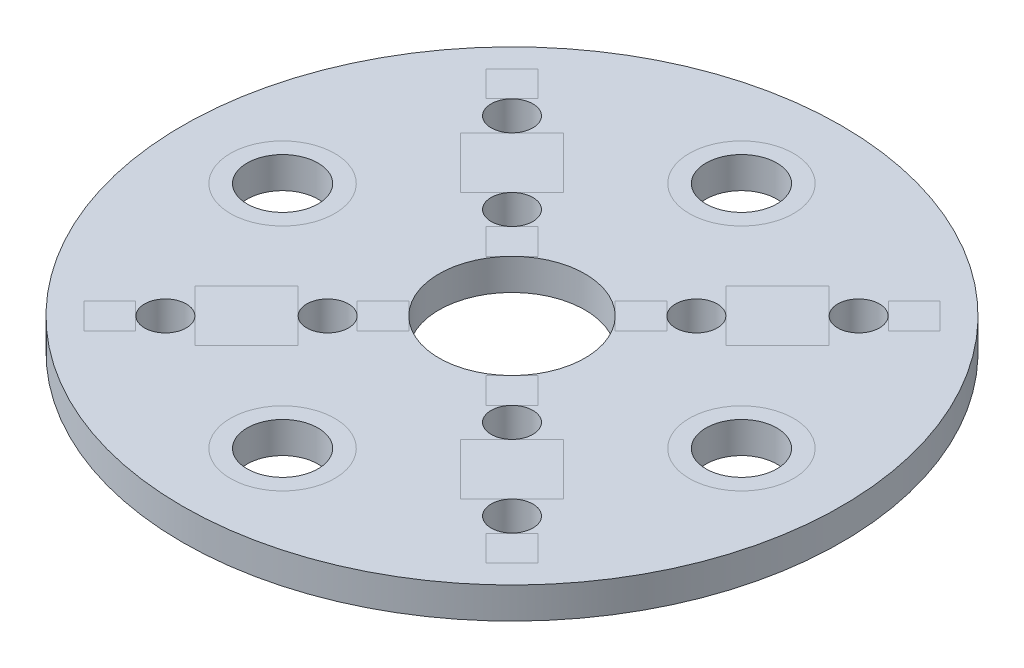
SolidWorks part; units mm, degrees
material "FR4 185HR (ISO)"
ref_plane "Front Plane" through (0, 0, 0) normal (0, 0, 1) x (1, 0, 0)
ref_plane "Top Plane" through (0, 0, 0) normal (0, 1, 0) x (1, 0, 0)
ref_plane "Right Plane" through (0, 0, 0) normal (1, 0, 0) x (0, 0, -1)
sketch "Sketch1" plane through (0, 0, 0) normal (0, 1, 0) x (1, 0, 0)
  line L0 (-3.75, -6.9532) -> (-3.75, -14.65)
  line L1 (-3.75, -14.65) -> (3.75, -14.65)
  line L2 (3.75, -14.65) -> (3.75, -6.9532)
  line L3 (0, 0) -> (0, -14.65) construction
  line L4 (0, 0) -> (7.9, 0) construction
  line L5 (-1.2374, 1.2374) -> (-5.5861, 5.5861) construction
  line L6 (-5.5, 0) -> (0, 5.5) construction
  line L7 (-1.4907, 5.3329) -> (-5.3329, 1.4907) construction
  line L8 (1.0607, -4.4393) -> (3.6352, -7.0139) construction
  line L9 (-1.0607, -4.4393) -> (-3.6352, -7.0139) construction
  line L10 (-4.4393, 1.0607) -> (-7.0139, 3.6352) construction
  line L11 (-4.4393, -1.0607) -> (-7.0139, -3.6352) construction
  line L12 (1.0607, 4.4393) -> (3.6352, 7.0139) construction
  line L13 (-1.0607, 4.4393) -> (-3.6352, 7.0139) construction
  line L14 (4.4393, -1.0607) -> (7.0139, -3.6352) construction
  line L15 (4.4393, 1.0607) -> (7.0139, 3.6352) construction
  line L16 (-2.6754, 2.0274) -> (-1.6291, -0.6392) construction
  line L17 (-2.0274, 2.6754) -> (0.6392, 1.6291) construction
  line L18 (-4.7962, 4.1481) -> (-6.3165, 4.7447) construction
  line L19 (-4.1481, 4.7962) -> (-4.7447, 6.3165) construction
  line L20 (1.2374, 1.2374) -> (5.5861, 5.5861) construction
  line L21 (0, 5.5) -> (5.5, 0) construction
  line L22 (5.3329, 1.4907) -> (1.4907, 5.3329) construction
  line L23 (1.2374, -1.2374) -> (5.5861, -5.5861) construction
  line L24 (5.5, 0) -> (0, -5.5) construction
  line L25 (1.4907, -5.3329) -> (5.3329, -1.4907) construction
  line L26 (-1.2374, -1.2374) -> (-5.5861, -5.5861) construction
  line L27 (0, -5.5) -> (-5.5, 0) construction
  line L28 (-5.3329, -1.4907) -> (-1.4907, -5.3329) construction
  line L29 (0, -10.75) -> (2.95, -10.75) construction
  line L30 (0, -10.75) -> (-2.95, -10.75) construction
  arc A0 (3.75, -6.9532) -> (-3.75, -6.9532) centre (0, 0) ccw
  circle A1 centre (5.5, 0) radius 1.5 construction
  circle A2 centre (5.5, 0) radius 0.85
  circle A3 centre (0, -5.5) radius 0.85
  circle A4 centre (0, -5.5) radius 1.5 construction
  circle A5 centre (-5.5, 0) radius 0.85
  circle A6 centre (-5.5, 0) radius 1.5 construction
  circle A7 centre (0, 5.5) radius 0.85
  circle A8 centre (0, 5.5) radius 1.5 construction
  circle A9 centre (0, 0) radius 1.75
  arc A10 (-3.75, -6.9532) -> (3.75, -6.9532) centre (0, 0) ccw construction
  circle A11 centre (-4.154, 4.154) radius 0.5
  circle A12 centre (-2.21, 2.21) radius 0.5
  circle A13 centre (4.154, 4.154) radius 0.5
  circle A14 centre (2.21, 2.21) radius 0.5
  circle A15 centre (4.154, -4.154) radius 0.5
  circle A16 centre (2.21, -2.21) radius 0.5
  circle A17 centre (-4.154, -4.154) radius 0.5
  circle A18 centre (-2.21, -2.21) radius 0.5
  circle A19 centre (-3, 0) radius 0.25
  circle A20 centre (-1.5, -10.75) radius 0.25
  circle A21 centre (3, 0) radius 0.25
  circle A22 centre (1.5, -10.75) radius 0.25
  circle A23 centre (-6.2, 2.25) radius 0.25
  circle A24 centre (0, -9.75) radius 0.25
  circle A25 centre (0, -7.75) radius 0.25
  circle A26 centre (-1, -8.75) radius 0.25
  circle A27 centre (1, -8.75) radius 0.25
  circle A28 centre (-5.9, 3.55) radius 0.25
  circle A29 centre (6.2, 2.25) radius 0.25
  circle A30 centre (5.9, 3.55) radius 0.25
  point P23 (0, 0)
  point P24 (-3.4118, 3.4118)
  point P47 (0, 0)
  point P92 (0, 0)
  point P114 (0, 0)
  point P117 (0, 0)
  dimension "D5" = 3
  dimension "D6" = 1.7
  dimension "D8" = 3.5
  dimension "D11" = 1
  dimension "D12" = 1
  dimension "D16" = 5.5
  dimension "D18" = 0.5
  dimension "D23" = 8.75
  dimension "D15" = 7.75
  dimension "D22" = 9.75
  dimension "D19" = 3.9
  dimension "D20" = 3
  dimension "D24" = 0.5
  dimension "D13" = 2.21
  dimension "D14" = 4.154
  dimension "D26" = 2.25
  dimension "D27" = 0.5
  dimension "D28" = 6.2
  dimension "D29" = 5.9
  dimension "D30" = 3.55
  dimension "D31" = 0.5
  dimension "D2" = 7.5
  dimension "D3" = 14.65
  dimension "D4" = 90
  dimension "D9" = 45
  dimension "D17" = 4
  dimension "D21" = 1.5
  dimension "D25" = 1
  dimension "D7" = 4
  dimension "D10" = 4
extrude "Boss-Extrude1" add sketch "Sketch1" along normal blind 0.75
sketch "Sketch2" plane through (0, 0.75, 0) normal (0, 1, 0) x (1, 0, 0)
  line L0 (-4.154, -4.154) -> (-2.21, -2.21) construction
  line L1 (-2.7577, -4.5962) -> (-1.7678, -3.6063)
  line L2 (-1.7678, -3.6063) -> (-3.1113, -2.2628)
  line L3 (-3.1113, -2.2628) -> (-4.1012, -3.2527)
  line L4 (-4.1012, -3.2527) -> (-2.7577, -4.5962)
  line L5 (4.154, -4.154) -> (-4.154, 4.154) construction
  line L6 (4.5962, 2.7577) -> (3.6063, 1.7678)
  line L7 (3.2527, 4.1012) -> (4.5962, 2.7577)
  line L8 (3.6063, 1.7678) -> (2.2628, 3.1113)
  line L9 (2.2628, 3.1113) -> (3.2527, 4.1012)
  line L10 (-2.2628, 3.1113) -> (-3.2527, 4.1012)
  line L11 (-3.2527, 4.1012) -> (-4.5962, 2.7577)
  line L12 (-4.5962, 2.7577) -> (-3.6063, 1.7678)
  line L13 (-3.6063, -2.7577) -> (-2.2628, -4.1012) construction
  line L14 (-3.6063, 1.7678) -> (-2.2628, 3.1113)
  line L15 (3.1113, -2.2628) -> (4.1012, -3.2527)
  line L16 (4.1012, -3.2527) -> (2.7577, -4.5962)
  line L17 (1.7678, -3.6063) -> (3.1113, -2.2628)
  line L18 (2.7577, -4.5962) -> (1.7678, -3.6063)
  point P22 (-3.182, -3.182)
  point P26 (0, 0)
  dimension "D1" = 1.4
  dimension "D2" = 1.9
  dimension "D3" = 1.3
  dimension "D4" = 2
extrude "Boss-Extrude2" [suppressed] add sketch "Sketch2" along normal blind 0.075 and the other way offset from surface 0.075
sketch "Sketch3" [suppressed] plane through (0, 0.575, 0) normal (0, 1, 0) x (1, 0, 0)
  line L0 (-3.8467, -3.38) -> (-2.984, -2.5173)
  line L1 (-2.984, -2.5173) -> (-2.5173, -2.984)
  line L2 (-2.5173, -2.984) -> (-3.38, -3.8467)
  line L3 (-3.38, -3.8467) -> (-3.8467, -3.38)
  line L4 (-4.1543, -4.1543) -> (-2.2097, -2.2097) construction
  line L5 (-3.4153, -2.9486) -> (-2.9486, -3.4153) construction
  line L6 (-2.7648, -4.4618) -> (-3.1891, -4.0376)
  line L7 (-3.1891, -4.0376) -> (-2.9062, -3.7547)
  line L8 (-2.9062, -3.7547) -> (-2.4819, -4.179)
  line L9 (-2.4819, -4.179) -> (-2.7648, -4.4618)
  line L10 (-2.7577, -4.5962) -> (-1.7678, -3.6062) construction
  line L11 (-2.185, -3.882) -> (-1.9021, -3.5992)
  line L12 (-2.6092, -3.4578) -> (-2.185, -3.882)
  line L13 (-1.9021, -3.5992) -> (-2.3264, -3.1749)
  line L14 (-2.3264, -3.1749) -> (-2.6092, -3.4578)
  line L15 (2.2097, -2.2097) -> (-2.2097, 2.2097) construction
  line L16 (4.179, 2.4819) -> (4.4618, 2.7648)
  line L17 (4.4618, 2.7648) -> (4.0376, 3.1891)
  line L18 (4.0376, 3.1891) -> (3.7547, 2.9062)
  line L19 (3.7547, 2.9062) -> (4.179, 2.4819)
  line L20 (3.882, 2.185) -> (3.5992, 1.9021)
  line L21 (3.4578, 2.6092) -> (3.882, 2.185)
  line L22 (3.5992, 1.9021) -> (3.1749, 2.3264)
  line L23 (3.1749, 2.3264) -> (3.4578, 2.6092)
  line L24 (2.5173, 2.984) -> (2.984, 2.5173)
  line L25 (2.984, 2.5173) -> (3.8467, 3.38)
  line L26 (3.8467, 3.38) -> (3.38, 3.8467)
  line L27 (3.38, 3.8467) -> (2.5173, 2.984)
  line L28 (2.7648, -4.4618) -> (3.1891, -4.0376)
  line L29 (3.1891, -4.0376) -> (2.9062, -3.7547)
  line L30 (2.9062, -3.7547) -> (2.4819, -4.179)
  line L31 (2.4819, -4.179) -> (2.7648, -4.4618)
  line L32 (2.6092, -3.4578) -> (2.185, -3.882)
  line L33 (2.3264, -3.1749) -> (2.6092, -3.4578)
  line L34 (1.9021, -3.5992) -> (2.3264, -3.1749)
  line L35 (2.185, -3.882) -> (1.9021, -3.5992)
  line L36 (2.5173, -2.984) -> (3.38, -3.8467)
  line L37 (3.38, -3.8467) -> (3.8467, -3.38)
  line L38 (3.8467, -3.38) -> (2.984, -2.5173)
  line L39 (2.984, -2.5173) -> (2.5173, -2.984)
  line L40 (-3.38, 3.8467) -> (-2.5173, 2.984)
  line L41 (-2.5173, 2.984) -> (-2.984, 2.5173)
  line L42 (-3.8467, 3.38) -> (-3.38, 3.8467)
  line L43 (-2.984, 2.5173) -> (-3.8467, 3.38)
  line L44 (-4.0376, 3.1891) -> (-3.7547, 2.9062)
  line L45 (-3.7547, 2.9062) -> (-4.179, 2.4819)
  line L46 (-4.4618, 2.7648) -> (-4.0376, 3.1891)
  line L47 (-4.179, 2.4819) -> (-4.4618, 2.7648)
  line L48 (-3.1749, 2.3264) -> (-3.4578, 2.6092)
  line L49 (-3.4578, 2.6092) -> (-3.882, 2.185)
  line L50 (-3.5992, 1.9021) -> (-3.1749, 2.3264)
  line L51 (-3.882, 2.185) -> (-3.5992, 1.9021)
  line L52 (4.1012, -3.2527) -> (3.1113, -2.2627) construction
  point P10 (-3.182, -3.182)
  point P64 (0, 0)
  dimension "D1" = 1.22
  dimension "D2" = 0.66
  dimension "D3" = 0.6
  dimension "D4" = 0.4
  dimension "D5" = 0.1
  dimension "D6" = 2
extrude "Boss-Extrude3" [suppressed] add sketch "Sketch3" along normal blind 0.05 and the other way offset from surface 0.05
sketch "Sketch4" plane through (0, 0.75, 0) normal (0, 1, 0) x (1, 0, 0)
  line L4 (0.9284, -1.5465) -> (1.5474, -2.1655)
  line L5 (-1.5465, -0.9284) -> (-2.1655, -1.5474)
  line L6 (0.9284, -1.5465) -> (1.5465, -0.9284)
  line L7 (3.8004, 3.8004) -> (4.154, 3.4469)
  line L8 (1.9462, 3.1809) -> (3.1831, 4.4178)
  line L9 (1.9462, 3.1809) -> (3.1809, 1.9462)
  line L10 (3.1831, 4.4178) -> (4.4178, 3.1831)
  line L11 (3.1809, 1.9462) -> (4.4178, 3.1831)
  line L12 (1.9462, 3.1809) -> (4.4178, 3.1831) construction
  line L13 (3.1831, 4.4178) -> (3.1809, 1.9462) construction
  line L14 (3.1809, -1.9462) -> (4.4178, -3.1831)
  line L15 (3.1809, -1.9462) -> (1.9462, -3.1809)
  line L16 (1.9462, -3.1809) -> (3.1831, -4.4178)
  line L17 (4.4178, -3.1831) -> (3.1831, -4.4178)
  line L18 (-1.9462, -3.1809) -> (-3.1831, -4.4178)
  line L19 (-1.9462, -3.1809) -> (-3.1809, -1.9462)
  line L20 (-3.1809, -1.9462) -> (-4.4178, -3.1831)
  line L21 (-3.1831, -4.4178) -> (-4.4178, -3.1831)
  line L22 (-3.1809, 1.9462) -> (-4.4178, 3.1831)
  line L23 (-3.1809, 1.9462) -> (-1.9462, 3.1809)
  line L24 (-1.9462, 3.1809) -> (-3.1831, 4.4178)
  line L25 (-4.4178, 3.1831) -> (-3.1831, 4.4178)
  line L26 (1.5474, -2.1655) -> (2.1655, -1.5474)
  line L27 (1.5465, -0.9284) -> (2.1655, -1.5474)
  line L28 (0.9284, -1.5465) -> (2.1655, -1.5474) construction
  line L29 (1.5474, -2.1655) -> (1.5465, -0.9284) construction
  line L30 (-1.5465, -0.9284) -> (-0.9284, -1.5465)
  line L31 (-0.9284, -1.5465) -> (-1.5474, -2.1655)
  line L32 (-2.1655, -1.5474) -> (-1.5474, -2.1655)
  line L33 (-0.9284, 1.5465) -> (-1.5474, 2.1655)
  line L34 (-0.9284, 1.5465) -> (-1.5465, 0.9284)
  line L35 (-1.5465, 0.9284) -> (-2.1655, 1.5474)
  line L36 (-1.5474, 2.1655) -> (-2.1655, 1.5474)
  line L37 (1.5465, 0.9284) -> (2.1655, 1.5474)
  line L38 (1.5465, 0.9284) -> (0.9284, 1.5465)
  line L39 (0.9284, 1.5465) -> (1.5474, 2.1655)
  line L40 (2.1655, 1.5474) -> (1.5474, 2.1655)
  line L41 (4.2034, -4.8215) -> (4.8215, -4.2034)
  line L42 (4.2034, -4.8215) -> (4.8224, -5.4405)
  line L43 (4.8224, -5.4405) -> (5.4405, -4.8224)
  line L44 (4.8215, -4.2034) -> (5.4405, -4.8224)
  line L45 (-4.8215, -4.2034) -> (-5.4405, -4.8224)
  line L46 (-4.8215, -4.2034) -> (-4.2034, -4.8215)
  line L47 (-4.2034, -4.8215) -> (-4.8224, -5.4405)
  line L48 (-5.4405, -4.8224) -> (-4.8224, -5.4405)
  line L49 (-4.2034, 4.8215) -> (-4.8224, 5.4405)
  line L50 (-4.2034, 4.8215) -> (-4.8215, 4.2034)
  line L51 (-4.8215, 4.2034) -> (-5.4405, 4.8224)
  line L52 (-4.8224, 5.4405) -> (-5.4405, 4.8224)
  line L53 (4.8215, 4.2034) -> (5.4405, 4.8224)
  line L54 (4.8215, 4.2034) -> (4.2034, 4.8215)
  line L55 (4.2034, 4.8215) -> (4.8224, 5.4405)
  line L56 (5.4405, 4.8224) -> (4.8224, 5.4405)
  circle A0 centre (5.5, 0) radius 1.25
  circle A1 centre (4.154, 4.154) radius 0.5 construction
  circle A2 centre (0, -5.5) radius 1.25
  circle A3 centre (-5.5, 0) radius 1.25
  circle A4 centre (0, 5.5) radius 1.25
  point P1 (1.5469, -1.5469)
  point P13 (3.182, 3.182)
  dimension "D4" = 4
  dimension "D1" = 4
  dimension "D2" = 4
  dimension "D3" = 4
split line "Split Line1"
sketch "Sketch5" plane through (0, 0.75, 0) normal (0, 1, 0) x (1, 0, 0)
  circle A0 centre (-5.9, 3.55) radius 0.25
  circle A1 centre (-6.2, 2.25) radius 0.25
  circle A2 centre (5.9, 3.55) radius 0.25
  circle A3 centre (6.2, 2.25) radius 0.25
  circle A4 centre (3, 0) radius 0.25
  circle A5 centre (-3, 0) radius 0.2891
  circle A6 centre (0, -7.75) radius 0.25
extrude "Boss-Extrude4" add sketch "Sketch5" against normal blind 0.75
sketch "Sketch6" plane through (0, 0.75, 0) normal (0, 1, 0) x (1, 0, 0)
  line L0 (-3.75, -6.9532) -> (-3.75, -14.65)
  line L1 (-3.75, -14.65) -> (3.75, -14.65)
  line L2 (3.75, -14.65) -> (3.75, -6.9532)
  circle A0 centre (0, 0) radius 7.9
extrude "Cut-Extrude1" cut sketch "Sketch6" against normal blind 0.75 contours A0 L0 L1 L2 region at (0, 0.75, 11.1157)
sketch "Sketch7" plane through (0, 0.75, 0) normal (0, 1, 0) x (1, 0, 0)
  line L0 (-4.154, 4.154) -> (4.154, -4.154)
  line L1 (-4.154, -4.154) -> (4.154, 4.154)
ref_plane "Plane1" through (0, 0, 0) normal (-0.7071, 0, 0.7071) x (0.7071, 0, 0.7071)
sketch "Sketch8" plane through (0, 0, 0) normal (0, -1, 0) x (1, 0, 0)
  line L0 (0.9344, -1.5421) -> (1.5531, -2.1608)
  line L1 (-1.5461, -0.9292) -> (-2.1651, -1.5482)
  line L2 (0.9344, -1.5421) -> (1.5531, -0.9234)
  line L4 (1.936, 3.1914) -> (3.1735, 4.4288)
  line L5 (1.936, 3.1914) -> (3.1735, 1.954)
  line L6 (3.1735, 4.4288) -> (4.4109, 3.1914)
  line L7 (3.1735, 1.954) -> (4.4109, 3.1914)
  line L8 (1.936, 3.1914) -> (4.4109, 3.1914) construction
  line L9 (3.1735, 4.4288) -> (3.1735, 1.954) construction
  line L10 (3.1813, -1.9471) -> (4.4182, -3.184)
  line L11 (3.1813, -1.9471) -> (1.9466, -3.1818)
  line L12 (1.9466, -3.1818) -> (3.1835, -4.4186)
  line L13 (4.4182, -3.184) -> (3.1835, -4.4186)
  line L14 (-1.9458, -3.1818) -> (-3.1827, -4.4186)
  line L15 (-1.9458, -3.1818) -> (-3.1805, -1.9471)
  line L16 (-3.1805, -1.9471) -> (-4.4174, -3.184)
  line L17 (-3.1827, -4.4186) -> (-4.4174, -3.184)
  line L18 (-3.1805, 1.9454) -> (-4.4174, 3.1822)
  line L19 (-3.1805, 1.9454) -> (-1.9458, 3.18)
  line L20 (-1.9458, 3.18) -> (-3.1827, 4.4169)
  line L21 (-4.4174, 3.1822) -> (-3.1827, 4.4169)
  line L22 (1.5531, -2.1608) -> (2.1718, -1.5421)
  line L23 (1.5531, -0.9234) -> (2.1718, -1.5421)
  line L24 (0.9344, -1.5421) -> (2.1718, -1.5421) construction
  line L25 (1.5531, -2.1608) -> (1.5531, -0.9234) construction
  line L26 (-1.5461, -0.9292) -> (-0.928, -1.5473)
  line L27 (-0.928, -1.5473) -> (-1.547, -2.1664)
  line L28 (-2.1651, -1.5482) -> (-1.547, -2.1664)
  line L29 (-0.928, 1.5456) -> (-1.547, 2.1646)
  line L30 (-0.928, 1.5456) -> (-1.5461, 0.9275)
  line L31 (-1.5461, 0.9275) -> (-2.1651, 1.5465)
  line L32 (-1.547, 2.1646) -> (-2.1651, 1.5465)
  line L33 (1.5469, 0.9275) -> (2.1659, 1.5465)
  line L34 (1.5469, 0.9275) -> (0.9288, 1.5456)
  line L35 (0.9288, 1.5456) -> (1.5478, 2.1646)
  line L36 (2.1659, 1.5465) -> (1.5478, 2.1646)
  line L37 (4.2038, -4.8223) -> (4.8219, -4.2042)
  line L38 (4.2038, -4.8223) -> (4.8228, -5.4414)
  line L39 (4.8228, -5.4414) -> (5.4409, -4.8232)
  line L40 (4.8219, -4.2042) -> (5.4409, -4.8232)
  line L41 (-4.8211, -4.2042) -> (-5.4401, -4.8232)
  line L42 (-4.8211, -4.2042) -> (-4.203, -4.8223)
  line L43 (-4.203, -4.8223) -> (-4.822, -5.4414)
  line L44 (-5.4401, -4.8232) -> (-4.822, -5.4414)
  line L45 (-4.203, 4.8206) -> (-4.822, 5.4396)
  line L46 (-4.203, 4.8206) -> (-4.8211, 4.2025)
  line L47 (-4.8211, 4.2025) -> (-5.4401, 4.8215)
  line L48 (-4.822, 5.4396) -> (-5.4401, 4.8215)
  line L49 (4.8219, 4.2025) -> (5.4409, 4.8215)
  line L50 (4.8219, 4.2025) -> (4.2038, 4.8206)
  line L51 (4.2038, 4.8206) -> (4.8228, 5.4396)
  line L52 (5.4409, 4.8215) -> (4.8228, 5.4396)
  circle A0 centre (5.5004, -0.0009) radius 1.25
  circle A1 centre (0.0004, -5.5009) radius 1.25
  circle A2 centre (-5.4996, -0.0009) radius 1.25
  circle A3 centre (0.0004, 5.4991) radius 1.25
  point P1 (1.5531, -1.5421)
  point P11 (3.1735, 3.1914)
  point P60 (0, 0)
  dimension "D1" = 1.75
  dimension "D3" = 0.875
  dimension "D4" = 0.875
split line "Split Line2"
